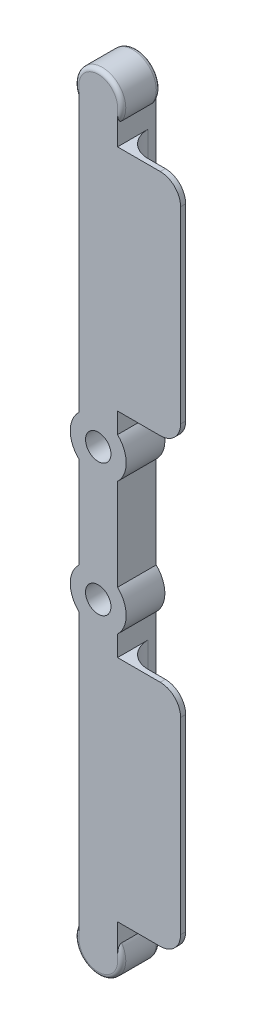
SolidWorks part; units mm, degrees
ref_plane "Front Plane" through (0, 0, 0) normal (0, 0, 1) x (1, 0, 0)
ref_plane "Top Plane" through (0, 0, 0) normal (0, 1, 0) x (1, 0, 0)
ref_plane "Right Plane" through (0, 0, 0) normal (1, 0, 0) x (0, 0, -1)
sketch "Sketch1" plane through (0, 0, 0) normal (0, 0, 1) x (1, 0, 0)
  line L0 (0, 0) -> (0, 44.9793) construction
  line L5 (3.8, 0) -> (-3.8, 0)
  line L6 (-3.8, 0) -> (-3.8, 6)
  line L7 (-3.8, 6) -> (-9.3, 6)
  line L8 (-9.3, 6) -> (-9.3, 9.28)
  line L9 (-9.3, 9.28) -> (-4.8, 13.8308)
  line L10 (-4.8, 13.8308) -> (4.8, 13.8308)
  line L11 (0, 13.8308) -> (0, 0) construction
  line L12 (9.3, 9.28) -> (4.8, 13.8308)
  line L13 (9.3, 6) -> (9.3, 9.28)
  line L14 (3.8, 6) -> (9.3, 6)
  line L15 (3.8, 0) -> (3.8, 6)
  line L17 (3.8, 0) -> (-3.8, 0)
  line L18 (3.8, 0) -> (3.8, -64)
  line L19 (3.8, -64) -> (-3.8, -64)
  line L20 (-3.8, 0) -> (-3.8, -64)
  line L21 (3.8, 0) -> (-3.8, -64) construction
  line L22 (3.8, -64) -> (-3.8, 0) construction
  circle A0 centre (0, 8.6308) radius 4.6218
  circle A1 centre (0, -51) radius 2.5
  arc A2 (3.8, -47.0238) -> (3.8, -54.9762) centre (0, -51) cw
  arc A3 (-3.8, -47.0238) -> (-3.8, -54.9762) centre (0, -51) ccw
  point P21 (0, -32)
  point P25 (3.8, -53.9708)
  dimension "D7" = 5.2
  dimension "D9" = 5
  dimension "D11" = 5.5
  dimension "D1" = 3.8
  dimension "D2" = 6
  dimension "D3" = 5.5
  dimension "D4" = 3.28
  dimension "D5" = 6.4
  dimension "D6" = 4.8
  dimension "D8" = 70
  dimension "D10" = 13
extrude "Boss-Extrude1" add sketch "Sketch1" along normal blind 7.6 contours A0 | A0 L6 L5 L15 | L5 L20 L19 L18 | A2 L18 | L20 A3 region at (0, -31.2007, 0) region at (0, 2.336, 0) region at (0, 8.6308, 0) region at (4.4899, -51, 0) region at (-4.4899, -51, 0)
ref_plane "Plane1" through (0, -64, 0) normal (0, -1, 0) x (-1, 0, 0)
sketch "Sketch4" plane through (0, 0, 7.6) normal (0, 0, 1) x (1, 0, 0)
  line L0 (0, 0) -> (0, -67.9118) construction
  line L1 (-3.8, -47.0238) -> (-3.8, 6) construction
  line L6 (-3.8, -43) -> (16.2, -43)
  line L7 (-3.8, -43) -> (-3.8, 2)
  line L8 (-3.8, 2) -> (16.2, 2)
  line L9 (16.2, -43) -> (16.2, 2)
  line L10 (-3.8, -43) -> (16.2, 2) construction
  line L11 (-3.8, 2) -> (16.2, -43) construction
  point P9 (6.2, -20.5)
  dimension "D1" = 20
  dimension "D2" = 45
  dimension "D3" = 2
extrude "Boss-Extrude2" add sketch "Sketch4" against normal blind 1
fillet "Fillet3" radius 0.8 2 edges at (0, 13.2526, 0) (0, 13.2526, 7.6)
fillet "Fillet2" radius 4 2 edges at (16.2, 2, 7.1) (16.2, -43, 7.1)
fillet "Fillet1" radius 5 1 edges at (3.8, -20.5, 6.6)
mirror "Mirror1" about plane through (0, -64, 0) normal (0, -1, 0) of "Fillet3", "Boss-Extrude2", "Fillet1", "Boss-Extrude1", "Fillet2"
